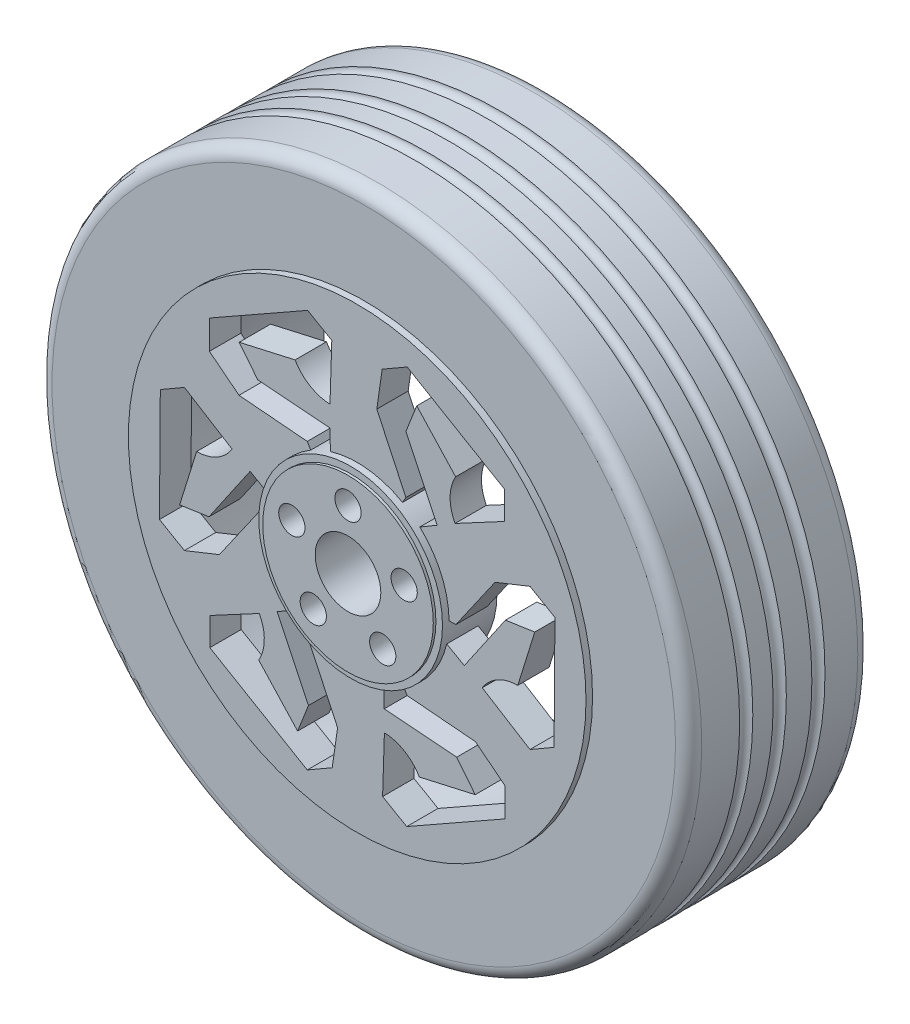
SolidWorks part; units mm, degrees
ref_plane "Front Plane" through (0, 0, 0) normal (0, 0, 1) x (1, 0, 0)
ref_plane "Top Plane" through (0, 0, 0) normal (0, 1, 0) x (1, 0, 0)
ref_plane "Right Plane" through (0, 0, 0) normal (1, 0, 0) x (0, 0, -1)
sketch "Sketch2" plane through (0, 0, 0) normal (0, 0, 1) x (1, 0, 0)
  circle A0 centre (0, 0) radius 247.55
  dimension "D1" = 495.1
extrude "Boss-Extrude1" add sketch "Sketch2" along normal blind 138.9
sketch "Sketch3" plane through (0, 0, 138.9) normal (0, 0, 1) x (1, 0, 0)
  circle A0 centre (0, 0) radius 174.35
  dimension "D1" = 348.7
fillet "Fillet1" radius 10 1 edges at (247.55, 0, 138.9)
fillet "Fillet2" radius 10 1 edges at (247.55, 0, 0)
extrude "Boss-Extrude2" add sketch "Sketch3" along normal blind 5
sketch "Sketch5" plane through (0, 0, 143.9) normal (0, 0, 1) x (1, 0, 0)
  line L0 (105.0037, 43.3694) -> (131.6337, 54.0214)
  line L1 (131.6337, 54.0214) -> (150.6653, 43.0319)
  line L2 (150.6653, 43.0319) -> (150.3446, -0.3609)
  line L3 (150.3446, -0.3609) -> (150.0291, -43.0412)
  line L4 (150.0291, -43.0412) -> (131.6404, -53.6579)
  line L5 (131.6404, -53.6579) -> (95.2902, -31.0843)
  line L7 (122.3632, -15.976) -> (135.2996, 25.6977)
  line L8 (135.2996, 25.6977) -> (112.9256, 22.3447)
  line L10 (112.9256, 22.3447) -> (81.5922, -23.3101)
  line L11 (81.5922, -23.3101) -> (40.2577, 0.1488)
  line L12 (40.2577, 0.1488) -> (75.1777, 0.5509)
  line L13 (75.1777, 0.5509) -> (105.0037, 43.3694)
  line L14 (90.0609, -69.2512) -> (112.6007, -86.9874)
  line L16 (112.6007, -86.9874) -> (112.5994, -108.964)
  line L17 (112.5994, -108.964) -> (74.8597, -130.3827)
  line L18 (74.8597, -130.3827) -> (37.7398, -151.4496)
  line L19 (37.7398, -151.4496) -> (19.3511, -140.8329)
  line L20 (19.3511, -140.8329) -> (20.7253, -98.0659)
  line L21 (47.346, -113.9577) -> (89.9046, -104.3241)
  line L22 (89.9046, -104.3241) -> (75.8138, -86.6241)
  line L23 (19.0329, 141.0088) -> (38.0659, 151.9959)
  line L24 (38.0659, 151.9959) -> (75.4849, 130.0217)
  line L25 (75.4849, 130.0217) -> (112.2893, 108.4084)
  line L26 (112.2893, 108.4084) -> (112.2893, 87.175)
  line L27 (112.2893, 87.175) -> (74.5649, 66.9816)
  line L28 (75.0173, 97.9817) -> (45.395, 130.0217)
  line L29 (45.395, 130.0217) -> (37.1117, 108.9688)
  line L30 (37.1117, 108.9688) -> (60.9833, 59.0059)
  line L31 (60.9833, 59.0059) -> (20, 34.9386)
  line L32 (20, 34.9386) -> (37.1117, 65.3813)
  line L33 (37.1117, 65.3813) -> (14.9428, 112.6206)
  line L34 (14.9428, 112.6206) -> (19.0329, 141.0088)
  line L35 (75.8138, -86.6241) -> (20.6089, -82.316)
  line L36 (20.6089, -82.316) -> (20.2577, -34.7898)
  line L37 (20.2577, -34.7898) -> (38.066, -64.8303)
  line L38 (38.066, -64.8303) -> (90.0609, -69.2512)
  line L39 (-14.9428, -112.6206) -> (-19.0329, -141.0088)
  line L40 (-19.0329, -141.0088) -> (-38.0659, -151.9959)
  line L41 (-38.0659, -151.9959) -> (-75.4849, -130.0217)
  line L42 (-75.4849, -130.0217) -> (-112.2893, -108.4084)
  line L43 (-112.2893, -108.4084) -> (-112.2893, -87.175)
  line L44 (-112.2893, -87.175) -> (-74.5649, -66.9816)
  line L45 (-75.0173, -97.9817) -> (-45.395, -130.0217)
  line L46 (-45.395, -130.0217) -> (-37.1117, -108.9687)
  line L47 (-37.1117, -108.9687) -> (-60.9833, -59.0059)
  line L48 (-60.9833, -59.0059) -> (-20, -34.9386)
  line L49 (-20, -34.9386) -> (-37.1117, -65.3812)
  line L50 (-37.1117, -65.3812) -> (-14.9428, -112.6206)
  line L51 (-105.0037, -43.3694) -> (-131.6337, -54.0214)
  line L52 (-131.6337, -54.0214) -> (-150.6653, -43.0319)
  line L53 (-150.6653, -43.0319) -> (-150.3446, 0.3609)
  line L54 (-150.3446, 0.3609) -> (-150.0291, 43.0412)
  line L55 (-150.0291, 43.0412) -> (-131.6404, 53.6579)
  line L56 (-131.6404, 53.6579) -> (-95.2902, 31.0843)
  line L57 (-122.3632, 15.976) -> (-135.2996, -25.6977)
  line L58 (-135.2996, -25.6977) -> (-112.9256, -22.3447)
  line L59 (-112.9256, -22.3447) -> (-81.5922, 23.3101)
  line L60 (-81.5922, 23.3101) -> (-40.2577, -0.1488)
  line L61 (-40.2577, -0.1488) -> (-75.1777, -0.5509)
  line L62 (-75.1777, -0.5509) -> (-105.0037, -43.3694)
  line L63 (-90.0609, 69.2512) -> (-112.6007, 86.9874)
  line L64 (-112.6007, 86.9874) -> (-112.5994, 108.964)
  line L65 (-112.5994, 108.964) -> (-74.8597, 130.3827)
  line L66 (-74.8597, 130.3827) -> (-37.7398, 151.4496)
  line L67 (-37.7398, 151.4496) -> (-19.3511, 140.8329)
  line L68 (-19.3511, 140.8329) -> (-20.7253, 98.0659)
  line L69 (-47.346, 113.9577) -> (-89.9046, 104.3241)
  line L70 (-89.9046, 104.3241) -> (-75.8138, 86.6241)
  line L71 (-75.8138, 86.6241) -> (-20.6089, 82.316)
  line L72 (-20.6089, 82.316) -> (-20.2577, 34.7898)
  line L73 (-20.2577, 34.7898) -> (-38.066, 64.8303)
  line L74 (-38.066, 64.8303) -> (-90.0609, 69.2512)
  arc A2 (74.5649, 66.9816) -> (75.0173, 97.9817) centre (102.7589, 82.0735) cw
  arc A3 (95.2902, -31.0843) -> (122.3632, -15.976) centre (122.4571, -47.955) cw
  arc A4 (20.7253, -98.0659) -> (47.346, -113.9577) centre (19.6983, -130.0285) cw
  arc A5 (-74.5649, -66.9816) -> (-75.0173, -97.9817) centre (-102.7589, -82.0735) cw
  arc A6 (-95.2902, 31.0843) -> (-122.3632, 15.976) centre (-122.4571, 47.955) cw
  arc A7 (-20.7253, 98.0659) -> (-47.346, 113.9577) centre (-19.6983, 130.0285) cw
  point P87 (0, 0)
  dimension "D1" = 6
sketch "Sketch6" plane through (0, 0, 143.9) normal (0, 0, 1) x (1, 0, 0)
sketch "Sketch8" plane through (0, 0, 143.9) normal (0, 0, 1) x (1, 0, 0)
extrude "Cut-Extrude1" cut sketch "Sketch5" against normal blind 30
sketch "Sketch9" plane through (0, 0, 143.9) normal (0, 0, 1) x (1, 0, 0)
  circle A0 centre (0, 0) radius 73.3512
sketch3d "3DSketch1" plane through (0, 0, 0) normal (0, 0, 1) x (1, 0, 0)
sketch3d "3DSketch2" plane through (0, 0, 0) normal (0, 0, 1) x (1, 0, 0)
sketch "Sketch14" plane through (0, 0, 95) normal (0, 0, 1) x (1, 0, 0)
  circle A0 centre (0, 0) radius 247.55
sketch "Sketch15" plane through (0, 0, 69.45) normal (0, 0, 1) x (1, 0, 0)
  circle A0 centre (0, 0) radius 247.55
sketch "Sketch16" plane through (0, 0, 40) normal (0, 0, 1) x (1, 0, 0)
  circle A0 centre (0, 0) radius 247.55
sketch3d "3DSketch3" plane through (0, 0, 0) normal (0, 0, 1) x (1, 0, 0)
sweep "Cut-Sweep1" cut path "Sketch16" circular profile diameter 10 parameters "D3"=10
sweep "Cut-Sweep2" cut path "Sketch15" circular profile diameter 10 parameters "D3"=10
sweep "Cut-Sweep3" cut path "Sketch14" circular profile diameter 10 parameters "D3"=10
sketch3d "3DSketch4"
  circle A0 centre (0, 0, 0) radius 25
  point P2 (0, 0, 25)
  dimension "D1" = 50
extrude "Cut-Extrude2" cut sketch "3DSketch4" along direction (0, 0, 1) on the side of the normal blind 179
sketch "Sketch22" plane through (0, 0, 0) normal (0, 0, -1) x (-1, 0, 0)
  circle A0 centre (0, 0) radius 140.4764
  dimension "D1" = 280.9527
sketch "Sketch23" plane through (0, 0, 0) normal (0, 0, -1) x (-1, 0, 0)
  circle A0 centre (0, 0) radius 169.35
  dimension "D1" = 338.7
extrude "Cut-Extrude4" cut sketch "Sketch23" against normal blind 120
sketch3d "3DSketch5" plane through (0, 0, 0) normal (0, 0, 1) x (1, 0, 0)
sketch3d "3DSketch6" plane through (0, 0, 0) normal (0, 0, 1) x (1, 0, 0)
  dimension "D1" = 10
sketch "Sketch105" plane through (0, 0, 120) normal (0, 0, -1) x (-1, 0, 0)
  circle A0 centre (0, 0) radius 72.1629
  circle A1 centre (0, 0) radius 25
sketch "Sketch113" plane through (0, 0, 143.9) normal (0, 0, 1) x (1, 0, 0)
  circle A0 centre (0, 0) radius 70
  dimension "D1" = 140
extrude "Boss-Extrude6" add sketch "Sketch113" against normal blind 36.503 and the other way blind 5
sketch "Sketch114" plane through (0, 0, 148.9) normal (0, 0, 1) x (1, 0, 0)
  circle A0 centre (0, 0) radius 65
  dimension "D1" = 130
extrude "Boss-Extrude7" add sketch "Sketch114" along normal blind 2
sketch "Sketch115" plane through (0, 0, 150.9) normal (0, 0, 1) x (1, 0, 0)
  line L0 (0, 25) -> (0, 65) construction
  circle A0 centre (0, 0) radius 25
  circle A1 centre (0, 0) radius 65 construction
  dimension "D1" = 50
extrude "Cut-Extrude6" cut sketch "Sketch115" against normal blind 82
sketch "Sketch116" plane through (0, 0, 150.9) normal (0, 0, 1) x (1, 0, 0)
  line L0 (0, 65) -> (0, 25) construction
  circle A0 centre (0, 0) radius 65 construction
  circle A1 centre (0, 0) radius 25 construction
  circle A2 centre (0, 45) radius 10
  circle A3 centre (42.7975, 13.9058) radius 10
  circle A4 centre (26.4503, -36.4058) radius 10
  circle A5 centre (-26.4503, -36.4058) radius 10
  circle A6 centre (-42.7975, 13.9058) radius 10
  point P20 (0, 0)
  dimension "D1" = 20
  dimension "D2" = 5
extrude "Cut-Extrude7" cut sketch "Sketch116" against normal blind 20
sketch "Sketch117" plane through (0, 0, 130.9) normal (0, 0, 1) x (1, 0, 0)
  line L0 (0, 25) -> (0, 65) construction
  circle A0 centre (0, 0) radius 25 construction
  circle A1 centre (0, 0) radius 65 construction
  circle A2 centre (0, 45) radius 5
  circle A3 centre (42.7975, 13.9058) radius 5
  circle A4 centre (26.4503, -36.4058) radius 5
  circle A5 centre (-26.4503, -36.4058) radius 5
  circle A6 centre (-42.7975, 13.9058) radius 5
  point P20 (0, 0)
  dimension "D1" = 10
  dimension "D2" = 5
extrude "Cut-Extrude8" cut sketch "Sketch117" against normal blind 30
